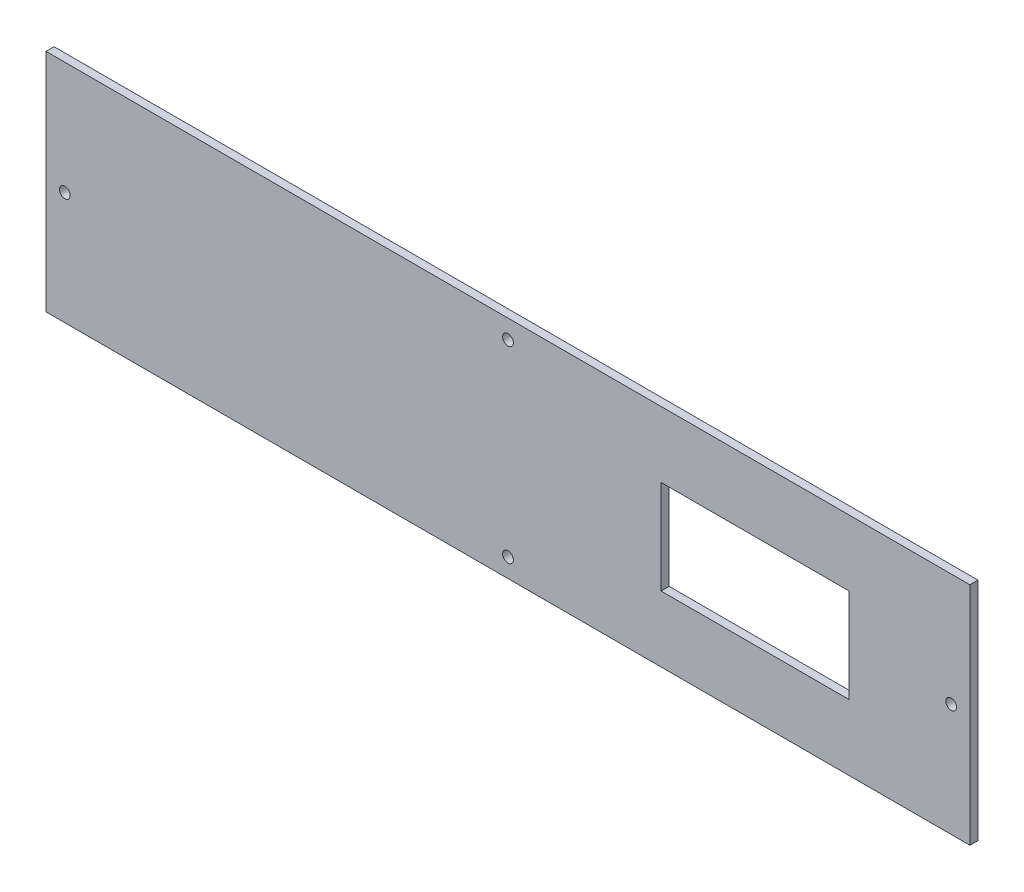
SolidWorks part; units mm, degrees
ref_plane "Piano frontale" through (0, 0, 0) normal (0, 0, 1) x (1, 0, 0)
ref_plane "Piano superiore" through (0, 0, 0) normal (0, 1, 0) x (1, 0, 0)
ref_plane "Piano destro" through (0, 0, 0) normal (1, 0, 0) x (0, 0, -1)
sketch "Schizzo1" plane through (0, 0, 0) normal (0, 0, 1) x (1, 0, 0)
  line L0 (0, 0) -> (0, 84)
  line L1 (0, 84) -> (344, 84)
  line L2 (344, 84) -> (344, 0)
  line L3 (344, 0) -> (0, 0)
  line L4 (0, 42) -> (344, 42) construction
  line L5 (172, 42) -> (172, 123.488) construction
  line L6 (229, 59.5) -> (229, 24.5)
  line L7 (229, 24.5) -> (299, 24.5)
  line L8 (299, 24.5) -> (299, 59.5)
  line L9 (299, 59.5) -> (229, 59.5)
  circle A0 centre (7, 42) radius 2
  circle A1 centre (172, 77) radius 2
  circle A2 centre (172, 7) radius 2
  circle A3 centre (337, 42) radius 2
  dimension "D3" = 7
  dimension "D4" = 7
  dimension "D6" = 4
  dimension "D1" = 84
  dimension "D2" = 344
  dimension "D5" = 45
  dimension "D7" = 70
  dimension "D8" = 35
extrude "Estrusione-Estrusione1" add sketch "Schizzo1" along normal blind 3
